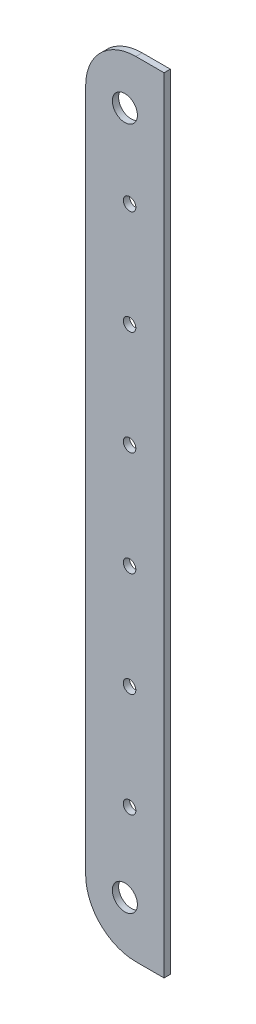
SolidWorks part; units mm, degrees
ref_plane "Front Plane" through (0, 0, 0) normal (0, 0, 1) x (1, 0, 0)
ref_plane "Top Plane" through (0, 0, 0) normal (0, 1, 0) x (1, 0, 0)
ref_plane "Right Plane" through (0, 0, 0) normal (1, 0, 0) x (0, 0, -1)
sketch "Sketch1" plane through (0, 0, 0) normal (0, 0, 1) x (1, 0, 0)
  line L0 (-12.5, 0) -> (12.5, 0) construction
  line L1 (3.5, 125) -> (12.5, 125)
  line L2 (-12.5, 109) -> (-12.5, -109)
  line L3 (3.5, -125) -> (12.5, -125)
  line L4 (12.5, 125) -> (12.5, -125)
  line L5 (-12.5, 125) -> (12.5, -125) construction
  line L6 (-12.5, -125) -> (12.5, 125) construction
  line L7 (-12.5, 109) -> (-12.5, 125) construction
  line L8 (-12.5, 125) -> (3.5, 125) construction
  line L9 (-12.5, 109) -> (-12.5, 125) construction
  circle A0 centre (0, 109) radius 4
  circle A1 centre (0, -109) radius 4
  arc A2 (3.5, 125) -> (-12.5, 109) centre (3.5, 109) ccw
  arc A3 (-12.5, -109) -> (3.5, -125) centre (3.5, -109) ccw
  point P0 (0, 0)
  dimension "D4" = 8
  dimension "D5" = 16
  dimension "D2" = 16
  dimension "D1" = 25
  dimension "D3" = 218
  dimension "D6" = 250
extrude "Boss-Extrude1" add sketch "Sketch1" along normal blind 2
sketch "Sketch2" plane through (0, 0, 2) normal (0, 0, 1) x (1, 0, 0)
  circle A0 centre (1.5, 83.3) radius 2
  circle A1 centre (1.5, 50) radius 2
  circle A2 centre (1.5, 16.7) radius 2
  circle A3 centre (1.5, -16.7) radius 2
  circle A4 centre (1.5, -50) radius 2
  circle A5 centre (1.5, -83.3) radius 2
extrude "Cut-Extrude1" cut sketch "Sketch2" against normal blind 2
